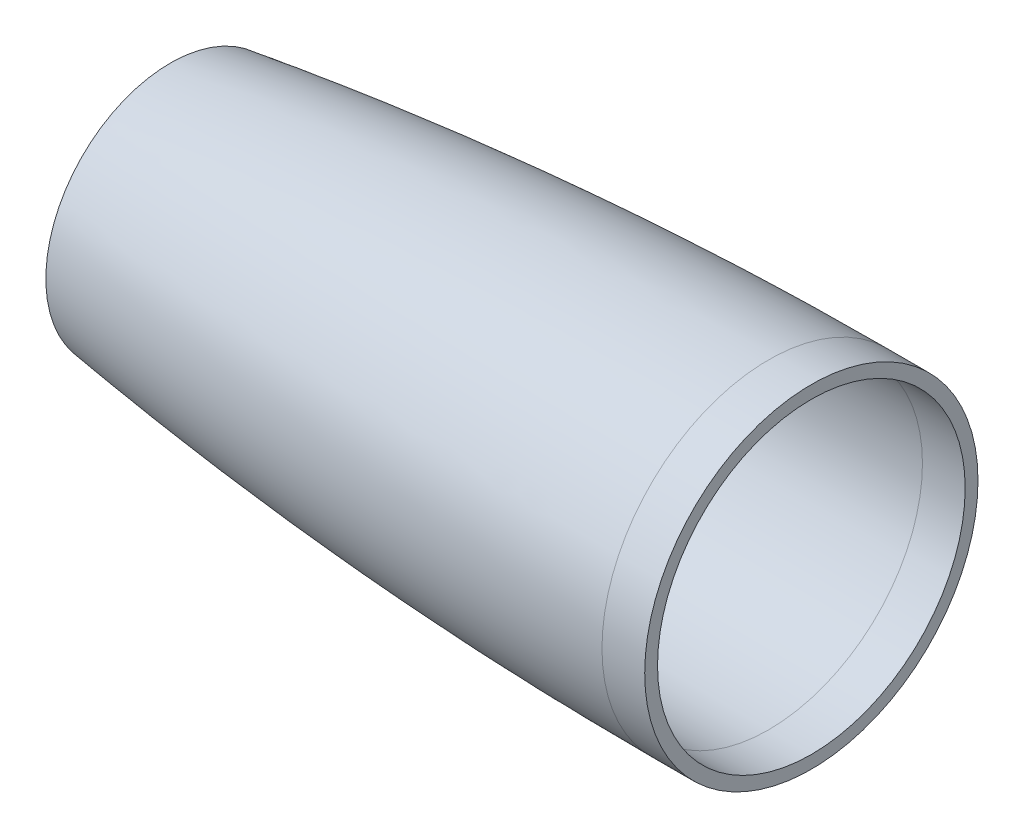
SolidWorks part; units mm, degrees
ref_plane "Front Plane" through (0, 0, 0) normal (0, 0, 1) x (1, 0, 0)
ref_plane "Top Plane" through (0, 0, 0) normal (0, 1, 0) x (1, 0, 0)
ref_plane "Right Plane" through (0, 0, 0) normal (1, 0, 0) x (0, 0, -1)
sketch "Sketch1" plane through (0, 0, 0) normal (0, 1, 0) x (1, 0, 0)
  line L0 (355.6, 50.8) -> (355.6, 1.27)
  line L1 (355.6, 1.27) -> (50.8, 1.27)
  line L2 (50.8, 13.6816) -> (50.8, 1.27)
  spline S0 degree 4 poles (21.2341, 5.9936) (21.856, 6.1634) (23.0998, 6.5019) (25.5843, 7.1746) (28.69, 8.0062) (31.7724, 8.8231) (34.8672, 9.6339) (37.2923, 10.2647) (39.7915, 10.9085) (42.145, 11.5111) (44.7925, 12.1812) (46.8566, 12.7019) (49.9381, 13.4687) (51.3469, 13.8173) (53.9013, 14.445) (55.9043, 14.9331) (57.9182, 15.4203) (59.9692, 15.9131) (62.0056, 16.3987) (64.0459, 16.8817) (66.6196, 17.4865) (69.7274, 18.2096) (73.3707, 19.0464) (77.5504, 19.9917) (82.7791, 21.1557) (97.434, 24.3488) (119.4856, 28.817) (168.0008, 37.516) (219.035, 44.0813) (262.8224, 47.8202) (299.2065, 49.5707) (308.8412, 49.9474) (315.2656, 50.1624) (319.549, 50.2912) (323.8328, 50.4056) (328.117, 50.5056) (332.4014, 50.5911) (336.1391, 50.6531) (339.3296, 50.6971) (341.9732, 50.7276) (344.0698, 50.7484) (346.1633, 50.7657) (348.2725, 50.7795) (350.3447, 50.7899) (352.4057, 50.7968) (355.0352, 50.8005) (356.4848, 50.8002) (359.6537, 50.7954) (361.7791, 50.7854) (364.5032, 50.7703) (366.9275, 50.7502) (369.503, 50.7251) (372.0018, 50.695) (374.5511, 50.6597) (377.0919, 50.6192) (379.6547, 50.5733) (382.2234, 50.522) (384.1523, 50.4796) (385.4374, 50.4496) (386.0799, 50.4342) knots 0 0 0 0 0 0.006986 0.013973 0.027946 0.034806 0.041666 0.048526 0.055386 0.062246 0.069106 0.075966 0.082827 0.088511 0.094195 0.099879 0.105563 0.111247 0.116931 0.122615 0.128299 0.139917 0.151536 0.163154 0.174773 0.19801 0.314194 0.407142 0.709223 0.755697 0.790552 0.802171 0.813789 0.825408 0.837026 0.848645 0.860263 0.871882 0.877566 0.88325 0.888934 0.894618 0.900302 0.905986 0.91167 0.917354 0.924199 0.931044 0.937889 0.944735 0.95158 0.958425 0.96527 0.972115 0.979087 0.986058 0.993029 1 1 1 1 1 construction
  spline S1 degree 4 poles (50.8, 13.6816) (51.2246, 13.7865) (52.0797, 13.9974) (53.9013, 14.445) (55.9043, 14.9331) (57.9182, 15.4203) (59.9692, 15.9131) (62.0056, 16.3987) (64.0459, 16.8817) (66.6196, 17.4865) (69.7274, 18.2096) (73.3707, 19.0464) (77.5504, 19.9917) (82.7791, 21.1557) (97.434, 24.3488) (119.4856, 28.817) (168.0008, 37.516) (219.035, 44.0813) (262.8224, 47.8202) (299.2065, 49.5707) (308.8412, 49.9474) (315.2656, 50.1624) (319.549, 50.2912) (323.8328, 50.4056) (328.117, 50.5056) (332.4014, 50.5911) (336.1391, 50.6531) (339.3296, 50.6971) (341.9732, 50.7276) (344.0698, 50.7484) (346.1633, 50.7657) (348.2725, 50.7795) (350.3447, 50.7899) (352.4057, 50.7968) (354.282, 50.7994) (355.1626, 50.8) (355.6, 50.8) knots 0.082827 0.082827 0.082827 0.082827 0.082827 0.088511 0.094195 0.099879 0.105563 0.111247 0.116931 0.122615 0.128299 0.139917 0.151536 0.163154 0.174773 0.19801 0.314194 0.407142 0.709223 0.755697 0.790552 0.802171 0.813789 0.825408 0.837026 0.848645 0.860263 0.871882 0.877566 0.88325 0.888934 0.894618 0.900302 0.905986 0.91167 0.917354 0.917354 0.917354 0.917354 0.917354
  dimension "D1" = 49.53
  dimension "D2" = 12.4116
revolve "Revolve2" add sketch "Sketch1" angle 360 about L1
ref_plane "Plane1" through (358.14, 0, 0) normal (1, 0, 0) x (0, 0, -1)
sketch "Sketch2" plane through (355.6, 0, 0) normal (1, 0, 0) x (0, 0, -1)
  line L1 (-48.26, 0) -> (50.8, 0) construction
  circle A0 centre (1.27, 0) radius 49.53 construction
  circle A1 centre (1.27, 0) radius 49.53
extrude "Boss-Extrude1" add sketch "Sketch2" along normal blind 203.2
sketch "Sketch3" plane through (50.8, 0, 0) normal (-1, 0, 0) x (0, 0, 1)
  line L0 (-13.6816, 0) -> (11.1416, 0) construction
  circle A0 centre (-1.27, 0) radius 12.4116 construction
  circle A1 centre (-1.27, 0) radius 12.4116
extrude "Boss-Extrude2" add sketch "Sketch3" along normal blind 50.8
ref_plane "Plane2" through (368.3, 0, 0) normal (1, 0, 0) x (0, 0, -1)
sketch "Sketch4" plane through (368.3, 0, 0) normal (1, 0, 0) x (0, 0, -1)
  line L0 (-48.26, 0) -> (50.8, 0) construction
  circle A0 centre (1.27, 0) radius 49.53 construction
  circle A1 centre (1.27, 0) radius 49.53
extrude "Cut-Extrude1" cut sketch "Sketch4" along normal blind 381
ref_plane "Plane3" through (177.8, 0, 0) normal (1, 0, 0) x (0, 0, -1)
sketch "Sketch5" plane through (177.8, 0, 0) normal (1, 0, 0) x (0, 0, -1)
  circle A0 centre (1.27, 0) radius 49.53
extrude "Cut-Extrude2" cut sketch "Sketch5" against normal blind 381
shell "Shell2" thickness 3.81 removed face at (368.3, 0, -50.8) removed face at (177.8, 0, -38.2924)
